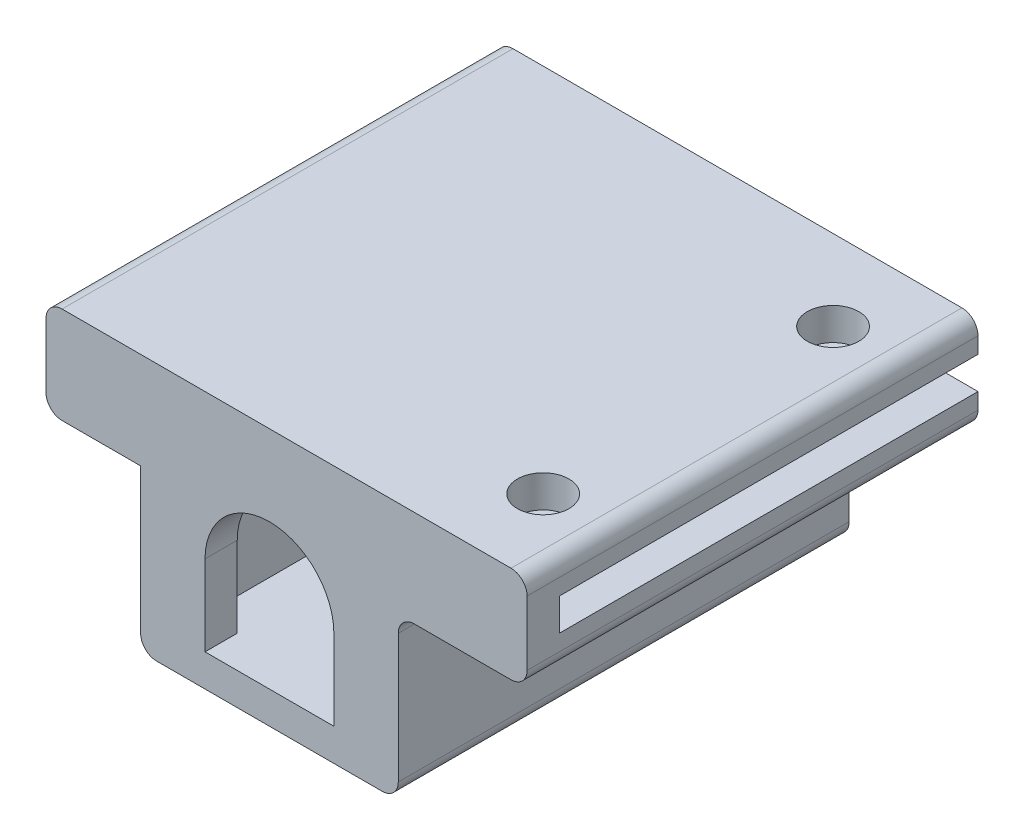
SolidWorks part; units mm, degrees
ref_plane "前视基准面" through (0, 0, 0) normal (0, 0, 1) x (1, 0, 0)
ref_plane "上视基准面" through (0, 0, 0) normal (0, 1, 0) x (1, 0, 0)
ref_plane "右视基准面" through (0, 0, 0) normal (1, 0, 0) x (0, 0, -1)
sketch "草图1" plane through (0, 0, 0) normal (0, 0, 1) x (1, 0, 0)
  line L0 (9, 3) -> (15, 3)
  line L1 (7, -7) -> (-7, -7)
  line L2 (8, -6) -> (8, 2)
  line L3 (8, 5) -> (-8, 5)
  line L4 (6, -4) -> (6, 4)
  line L5 (5, 5) -> (-5, 5)
  line L6 (-6, 4) -> (-6, -4)
  line L7 (-5, -5) -> (5, -5)
  line L8 (6, -4) -> (6, 4)
  line L9 (5, 5) -> (-5, 5)
  line L10 (-6, 4) -> (-6, -4)
  line L11 (-5, -5) -> (5, -5)
  line L12 (88.125, 7) -> (-11.875, 7)
  line L13 (-11.875, 7) -> (-11.875, 5)
  line L14 (-11.875, 5) -> (88.125, 5)
  line L15 (88.125, 5) -> (88.125, 7)
  line L16 (88.125, 7) -> (-11.875, 7)
  line L17 (-11.875, 7) -> (-11.875, 5)
  line L18 (-11.875, 5) -> (88.125, 5)
  line L19 (88.125, 5) -> (88.125, 7)
  line L20 (-8, -6) -> (-8, 3)
  line L21 (-12.875, 3) -> (-8, 3)
  line L22 (-13.875, 4) -> (-13.875, 8)
  line L23 (-12.875, 9) -> (15, 9)
  line L24 (16, 4) -> (16, 8)
  line L26 (4, 0) -> (4, -5)
  line L27 (4, -5) -> (-4, -5)
  line L28 (-4, 0) -> (-4, -5)
  arc A0 (4, 0) -> (-4, 0) centre (0, 0) ccw
  arc A1 (15, 9) -> (16, 8) centre (15, 8) cw
  arc A2 (8, 2) -> (9, 3) centre (9, 2) cw
  arc A3 (16, 4) -> (15, 3) centre (15, 4) cw
  arc A4 (6, 4) -> (5, 5) centre (5, 4) ccw
  arc A5 (-5, 5) -> (-6, 4) centre (-5, 4) ccw
  arc A6 (-6, -4) -> (-5, -5) centre (-5, -4) ccw
  arc A7 (5, -5) -> (6, -4) centre (5, -4) ccw
  arc A8 (6, 4) -> (5, 5) centre (5, 4) ccw
  arc A9 (-5, 5) -> (-6, 4) centre (-5, 4) ccw
  arc A10 (-6, -4) -> (-5, -5) centre (-5, -4) ccw
  arc A11 (5, -5) -> (6, -4) centre (5, -4) ccw
  arc A12 (8, -6) -> (7, -7) centre (7, -6) cw
  arc A13 (-7, -7) -> (-8, -6) centre (-7, -6) cw
  arc A14 (-13.875, 8) -> (-12.875, 9) centre (-12.875, 8) cw
  arc A15 (-12.875, 3) -> (-13.875, 4) centre (-12.875, 4) cw
  dimension "D3" = 1
  dimension "D5" = 2
  dimension "D6" = 2
  dimension "D1" = 0
  dimension "D2" = 0
extrude "凸台-拉伸1" add sketch "草图1" along normal blind 2 contours A11 L11 A10 L10 A9 L3 L18 L17 L16 L24 L23 L22 L21 L20 L1 L2 L0 A8 L8 | L18 L24 L16 L17 L3 | L11 A11 L8 A8 L3 A9 L10 A10 L28 A0 L26 region at (8.0533, 2.9467, 0) region at (2.0625, 6, 0) region at (5.5967, 4.5967, 0)
sketch "草图2" plane through (0, 0, 0) normal (0, 0, -1) x (-1, 0, 0)
  line L1 (6, -5) -> (-6, -5)
  line L2 (6, -5) -> (6, 5)
  line L3 (6, 5) -> (-6, 5)
  line L4 (-6, 4) -> (-6, -4)
  line L5 (5, 5) -> (-5, 5)
  line L6 (6, -4) -> (6, 4)
  line L7 (-5, -5) -> (5, -5)
  line L8 (-6, 4) -> (-6, -4)
  line L9 (5, 5) -> (-5, 5)
  line L10 (6, -4) -> (6, 4)
  line L11 (-5, -5) -> (5, -5)
  line L12 (-16, 8) -> (-16, 4)
  line L13 (-15, 3) -> (-9, 3)
  line L14 (-8, 2) -> (-8, -6)
  line L15 (-7, -7) -> (7, -7)
  line L16 (8, -6) -> (8, 3)
  line L17 (8, 3) -> (12.875, 3)
  line L18 (13.875, 4) -> (13.875, 8)
  line L19 (12.875, 9) -> (-15, 9)
  line L23 (11.875, 7) -> (-88.125, 7)
  line L24 (-16, 8) -> (-16, 4)
  line L25 (-15, 3) -> (-9, 3)
  line L26 (-8, 2) -> (-8, -6)
  line L27 (-7, -7) -> (7, -7)
  line L28 (8, -6) -> (8, 3)
  line L29 (8, 3) -> (12.875, 3)
  line L30 (13.875, 4) -> (13.875, 8)
  line L31 (12.875, 9) -> (-15, 9)
  line L36 (-6, -5) -> (-6, 5)
  line L37 (11.875, 5) -> (11.875, 7)
  line L38 (-88.125, 5) -> (11.875, 5)
  line L39 (-88.125, 7) -> (-88.125, 5)
  line L40 (11.875, 7) -> (-88.125, 7)
  line L41 (11.875, 5) -> (11.875, 7)
  line L42 (-88.125, 5) -> (11.875, 5)
  line L43 (-88.125, 7) -> (-88.125, 5)
  arc A4 (-5, 5) -> (-6, 4) centre (-5, 4) ccw
  arc A5 (6, 4) -> (5, 5) centre (5, 4) ccw
  arc A6 (5, -5) -> (6, -4) centre (5, -4) ccw
  arc A7 (-6, -4) -> (-5, -5) centre (-5, -4) ccw
  arc A8 (-5, 5) -> (-6, 4) centre (-5, 4) ccw
  arc A9 (6, 4) -> (5, 5) centre (5, 4) ccw
  arc A10 (5, -5) -> (6, -4) centre (5, -4) ccw
  arc A11 (-6, -4) -> (-5, -5) centre (-5, -4) ccw
  arc A15 (-16, 4) -> (-15, 3) centre (-15, 4) ccw
  arc A16 (-16, 4) -> (-15, 3) centre (-15, 4) ccw
  arc A17 (-8, 2) -> (-9, 3) centre (-9, 2) ccw
  arc A18 (-8, 2) -> (-9, 3) centre (-9, 2) ccw
  arc A19 (-8, -6) -> (-7, -7) centre (-7, -6) ccw
  arc A20 (-8, -6) -> (-7, -7) centre (-7, -6) ccw
  arc A21 (7, -7) -> (8, -6) centre (7, -6) ccw
  arc A22 (7, -7) -> (8, -6) centre (7, -6) ccw
  arc A23 (12.875, 3) -> (13.875, 4) centre (12.875, 4) ccw
  arc A24 (12.875, 3) -> (13.875, 4) centre (12.875, 4) ccw
  arc A25 (13.875, 8) -> (12.875, 9) centre (12.875, 8) ccw
  arc A26 (13.875, 8) -> (12.875, 9) centre (12.875, 8) ccw
  arc A27 (-15, 9) -> (-16, 8) centre (-15, 8) ccw
  arc A28 (-15, 9) -> (-16, 8) centre (-15, 8) ccw
  line M21 (4, -5) -> (-4, -5)
  line M25 (-16, 8) -> (-16, 4)
  line M26 (-15, 3) -> (-9, 3)
  line M27 (-8, 2) -> (-8, -6)
  line M28 (-7, -7) -> (7, -7)
  line M29 (8, -6) -> (8, 3)
  line M30 (8, 3) -> (12.875, 3)
  line M31 (13.875, 4) -> (13.875, 8)
  line M32 (12.875, 9) -> (-15, 9)
  line M33 (-16, 8) -> (-16, 4)
  dimension "D1" = 0
  dimension "D2" = 0
  dimension "D3" = 0
extrude "凸台-拉伸2" add sketch "草图2" along normal offset from surface (26 mm away) 2 contours L1 L36 L8 L2 M25 M26 M27 M28 M29 M30 M31 M32 M33 M21 region at (-6.3389, -4.5, 0) offset beyond the face yes
sketch "草图3" plane through (0, 0, -26) normal (0, 0, -1) x (-1, 0, 0)
  line L1 (6, -5) -> (-6, -5)
  line L2 (6, -5) -> (6, -4)
  line L3 (6, -4) -> (-6, -4)
  line L4 (-6, -5) -> (-6, -4)
  line L20 (-16, 5) -> (-16, 4)
  line L21 (-15, 3) -> (-9, 3)
  line L22 (-8, 2) -> (-8, -6)
  line L23 (-7, -7) -> (7, -7)
  line L24 (8, -6) -> (8, 3)
  line L25 (8, 3) -> (12.875, 3)
  line L26 (13.875, 4) -> (13.875, 8)
  line L27 (12.875, 9) -> (-15, 9)
  line L28 (6, 5) -> (6, -5)
  line L29 (6, 5) -> (6, -5)
  line L30 (6, -5) -> (-6, -5)
  line L31 (6, -5) -> (-6, -5)
  line L37 (-15, 3) -> (-9, 3)
  line L38 (-8, 2) -> (-8, -6)
  line L39 (-7, -7) -> (7, -7)
  line L40 (8, -6) -> (8, 3)
  line L41 (8, 3) -> (12.875, 3)
  line L42 (13.875, 4) -> (13.875, 8)
  line L43 (12.875, 9) -> (-15, 9)
  line L48 (-6, -5) -> (-6, 5)
  line L49 (-6, -5) -> (-6, 5)
  line L50 (-6, 5) -> (-16, 5)
  line L51 (-6, 5) -> (-16, 5)
  line L52 (-16, 8) -> (-16, 7)
  line L53 (-16, 8) -> (-16, 7)
  line L54 (-16, 7) -> (11.875, 7)
  line L55 (-16, 7) -> (11.875, 7)
  line L56 (11.875, 7) -> (11.875, 5)
  line L57 (11.875, 7) -> (11.875, 5)
  line L58 (11.875, 5) -> (6, 5)
  line L59 (11.875, 5) -> (6, 5)
  line L60 (-16, 5) -> (-16, 4)
  arc A7 (-16, 4) -> (-15, 3) centre (-15, 4) ccw
  arc A8 (-16, 4) -> (-15, 3) centre (-15, 4) ccw
  arc A9 (-8, 2) -> (-9, 3) centre (-9, 2) ccw
  arc A10 (-8, 2) -> (-9, 3) centre (-9, 2) ccw
  arc A11 (-8, -6) -> (-7, -7) centre (-7, -6) ccw
  arc A12 (-8, -6) -> (-7, -7) centre (-7, -6) ccw
  arc A13 (7, -7) -> (8, -6) centre (7, -6) ccw
  arc A14 (7, -7) -> (8, -6) centre (7, -6) ccw
  arc A15 (12.875, 3) -> (13.875, 4) centre (12.875, 4) ccw
  arc A16 (12.875, 3) -> (13.875, 4) centre (12.875, 4) ccw
  arc A17 (13.875, 8) -> (12.875, 9) centre (12.875, 8) ccw
  arc A18 (13.875, 8) -> (12.875, 9) centre (12.875, 8) ccw
  arc A19 (-15, 9) -> (-16, 8) centre (-15, 8) ccw
  arc A20 (-15, 9) -> (-16, 8) centre (-15, 8) ccw
  line M19 (6, 5) -> (6, -5)
  line M20 (6, -5) -> (-6, -5)
  line M21 (-6, -5) -> (-6, 5)
  dimension "D2" = 1
  dimension "D1" = 0
extrude "凸台-拉伸3" add sketch "草图3" against normal blind 1.6 contours L3 M19 M21 M20 region at (0, -4.5, -26)
sketch "草图4" plane through (0, 3, 0) normal (0, -1, 0) x (1, 0, 0)
  line L0 (12, -26) -> (12, 2) construction
  line L2 (12, -17.5359) -> (9, -19.2679)
  line L3 (9, -19.2679) -> (9, -22.7321)
  line L4 (9, 2) -> (9, -26)
  line L5 (9, -26) -> (15, -26)
  line L6 (15, -26) -> (15, 2)
  line L7 (15, 2) -> (9, 2)
  line L8 (9, 2) -> (9, -26)
  line L9 (9, -26) -> (15, -26)
  line L10 (15, -26) -> (15, 2)
  line L11 (15, 2) -> (9, 2)
  line L12 (9, -22.7321) -> (12, -24.4641)
  line L13 (12, -24.4641) -> (15, -22.7321)
  line L14 (15, -22.7321) -> (15, -19.2679)
  line L15 (15, -19.2679) -> (12, -17.5359)
  line L16 (15, -1.2679) -> (12, 0.4641)
  line L17 (12, 0.4641) -> (9, -1.2679)
  line L18 (9, -1.2679) -> (9, -4.7321)
  line L19 (9, -4.7321) -> (12, -6.4641)
  line L20 (12, -6.4641) -> (15, -4.7321)
  line L21 (15, -4.7321) -> (15, -1.2679)
  circle A0 centre (12, -21) radius 3 construction
  circle A1 centre (12, -3) radius 3 construction
  line M9 (9, 2) -> (9, -26)
  dimension "D2" = 6
  dimension "D3" = 6
  dimension "D4" = 5
  dimension "D5" = 5
  dimension "D1" = 0
extrude "切除-拉伸1" cut sketch "草图4" against normal blind 1 and the other way through all contours L10 L15 L2 L12 L13 M9 | L19 L20 L10 L16 L17 L8 region at (12, 3, -21) region at (12, 3, -3)
sketch "草图5" plane through (0, 4, 0) normal (0, -1, 0) x (1, 0, 0)
  line L0 (9, -19.2679) -> (15, -22.7321) construction
  line L1 (9, -1.2679) -> (15, -4.7321) construction
  line L6 (15, -22.7321) -> (15, -19.2679)
  line L7 (15, -19.2679) -> (12, -17.5359)
  line L8 (12, -17.5359) -> (9, -19.2679)
  line L9 (9, -19.2679) -> (9, -22.7321)
  line L10 (9, -22.7321) -> (12, -24.4641)
  line L11 (12, -24.4641) -> (15, -22.7321)
  line L12 (15, -22.7321) -> (15, -19.2679)
  line L13 (15, -19.2679) -> (12, -17.5359)
  line L14 (12, -17.5359) -> (9, -19.2679)
  line L15 (9, -19.2679) -> (9, -22.7321)
  line L16 (9, -22.7321) -> (12, -24.4641)
  line L17 (12, -24.4641) -> (15, -22.7321)
  line L18 (9, -4.7321) -> (12, -6.4641)
  line L19 (12, -6.4641) -> (15, -4.7321)
  line L20 (15, -4.7321) -> (15, -1.2679)
  line L21 (15, -1.2679) -> (12, 0.4641)
  line L22 (12, 0.4641) -> (9, -1.2679)
  line L23 (9, -1.2679) -> (9, -4.7321)
  line L24 (9, -4.7321) -> (12, -6.4641)
  line L25 (12, -6.4641) -> (15, -4.7321)
  line L26 (15, -4.7321) -> (15, -1.2679)
  line L27 (15, -1.2679) -> (12, 0.4641)
  line L28 (12, 0.4641) -> (9, -1.2679)
  line L29 (9, -1.2679) -> (9, -4.7321)
  circle A0 centre (12, -21) radius 1.6
  circle A1 centre (12, -3) radius 1.6
  dimension "D3" = 3.2
  dimension "D4" = 3.2
  dimension "D1" = 0
  dimension "D2" = 0
extrude "切除-拉伸2" cut sketch "草图5" against normal through all contours A0 | A1 region at (12, 4, -21) region at (12, 4, -3)
